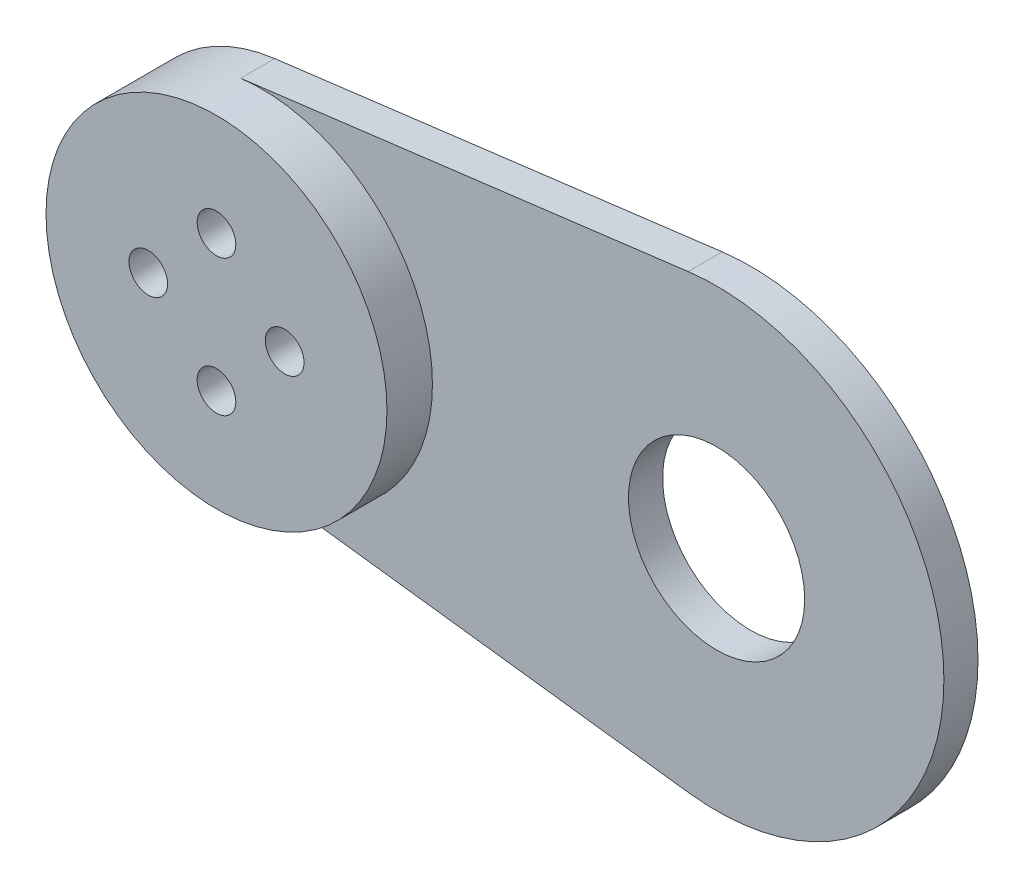
SolidWorks part; units mm, degrees
ref_plane "Front Plane" through (0, 0, 0) normal (0, 0, 1) x (1, 0, 0)
ref_plane "Top Plane" through (0, 0, 0) normal (0, 1, 0) x (1, 0, 0)
ref_plane "Right Plane" through (0, 0, 0) normal (1, 0, 0) x (0, 0, -1)
ref_plane "Plane1" through (0, 0, 3) normal (0, 0, 1) x (1, 0, 0)
sketch "Sketch1" plane through (0, 0, 3) normal (0, 0, 1) x (1, 0, 0)
  line L0 (-42.8105, 40.8003) -> (-82.1855, 35.8395)
  line L1 (-82.1855, 6.0748) -> (-42.8105, 1.114)
  arc A0 (-82.1855, 35.8395) -> (-82.1855, 6.0748) centre (-80.3105, 20.9572) ccw
  arc A1 (-42.8105, 1.114) -> (-42.8105, 40.8003) centre (-40.3105, 20.9572) ccw
  circle A2 centre (-40.3105, 20.9572) radius 7.75
  dimension "D1" = 20
  dimension "D2" = 15
  dimension "D4" = 15.5
  dimension "D3" = 40
extrude "Boss-Extrude1" add sketch "Sketch1" against normal blind 3
sketch "Sketch2" plane through (0, 0, 3) normal (0, 0, 1) x (1, 0, 0)
  line L0 (-80.3105, 20.9572) -> (-90.7953, 20.9572) construction
  circle A0 centre (-80.3105, 20.9572) radius 15
  circle A1 centre (-86.3105, 20.9572) radius 1.7
  circle A2 centre (-80.3105, 26.9572) radius 1.7
  circle A3 centre (-74.3105, 20.9572) radius 1.7
  circle A4 centre (-80.3105, 14.9572) radius 1.7
  point P14 (-80.3105, 20.9572)
  dimension "D1" = 6
  dimension "D3" = 3.4
  dimension "D2" = 4
extrude "Boss-Extrude2" add sketch "Sketch2" along normal blind 4 contours A0 A4 A3 A2 A1 | L0 A1 | A1 L0 | A2 | A3 | A4 region at (-86.3105, 20.2357, 3) region at (-86.3105, 21.6787, 3) region at (-70.6695, 10.0254, 3) region at (-80.3105, 26.9572, 3) region at (-74.3105, 20.9572, 3) region at (-80.3105, 14.9572, 3)
extrude "Cut-Extrude1" cut sketch "Sketch2<3>" against normal through all both and the other way through all contours A2 | A3 | A4 | A1
sketch "Sketch2<3>" plane through (0, 0, 3) normal (0, 0, 1) x (1, 0, 0) same geometry as "Sketch2"
